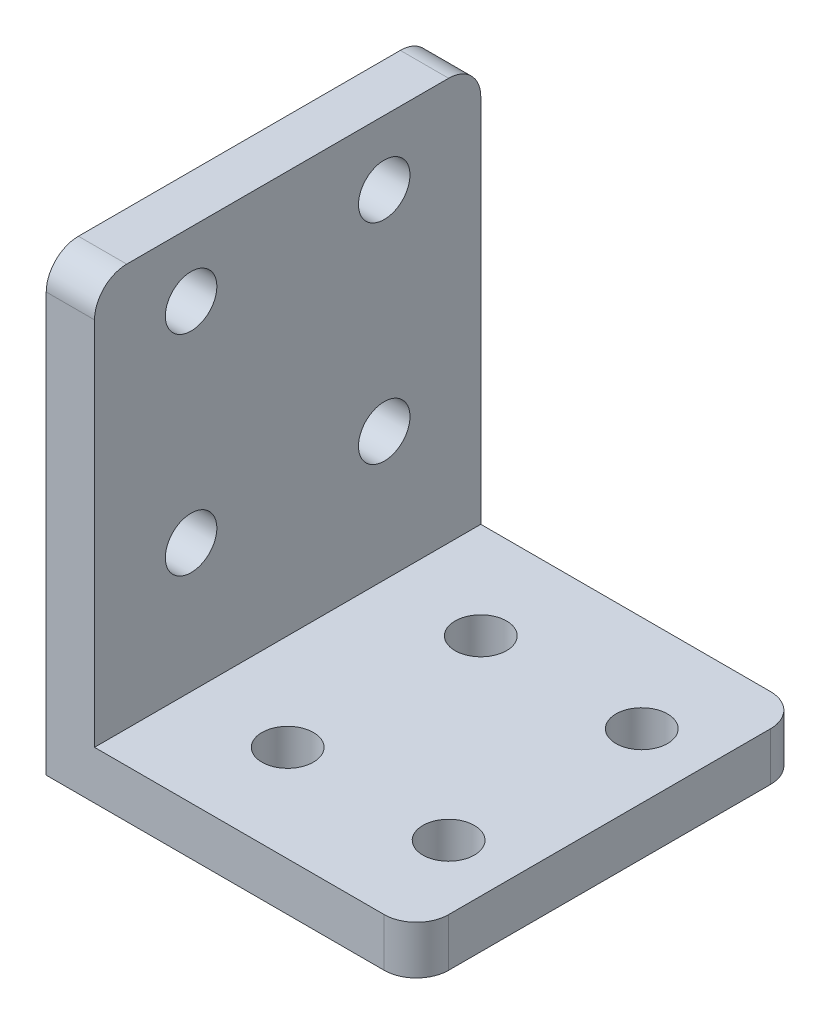
SolidWorks part; units mm, degrees
ref_plane "前视基准面" through (0, 0, 0) normal (0, 0, 1) x (1, 0, 0)
ref_plane "上视基准面" through (0, 0, 0) normal (0, 1, 0) x (1, 0, 0)
ref_plane "右视基准面" through (0, 0, 0) normal (1, 0, 0) x (0, 0, -1)
sketch "草图1" plane through (0, 0, 0) normal (0, 0, 1) x (1, 0, 0)
  line L0 (3, 231.6916) -> (3, 101.6916) construction
  line L1 (3, 129.6916) -> (6, 129.6916)
  line L2 (3, 129.6916) -> (3, -64.3846)
  line L4 (6, 129.6916) -> (6, 104.6916)
  line L6 (3, 101.6916) -> (26, 101.6916)
  line L7 (3, 101.6916) -> (3, -61.5122)
  line L8 (6, 104.6916) -> (26, 104.6916)
  line L9 (26, 101.6916) -> (26, 104.6916)
  dimension "D1" = 3
  dimension "D2" = 3
  dimension "D3" = 25
  dimension "D4" = 20
extrude "凸台-拉伸1" add sketch "草图1" against normal blind 24 contours L6 L9 L8 L4 L1 L2 L7 region at (4.5, 129.3293, 0)
sketch "草图2" plane through (6, 0, 0) normal (1, 0, 0) x (0, 0, -1)
  line L0 (24, 129.6916) -> (0, 129.6916) construction
  line L1 (0, 129.6916) -> (0, 104.6916) construction
  line L2 (24, 129.6916) -> (24, 104.6916) construction
  circle A0 centre (6, 125.6916) radius 1.6
  circle A1 centre (18, 125.6916) radius 1.6
  dimension "D1" = 3.2
  dimension "D2" = 3.2
  dimension "D3" = 4
  dimension "D4" = 6
  dimension "D5" = 6
  dimension "D6" = 4
extrude "切除-拉伸1" cut sketch "草图2" against normal blind 24
sketch "草图3" plane through (0, 104.6916, 0) normal (0, 1, 0) x (1, 0, 0)
  line L0 (26, 24) -> (26, 0) construction
  line L1 (6, 0) -> (26, 0) construction
  line L2 (6, 24) -> (26, 24) construction
  circle A0 centre (22, 6) radius 1.6
  circle A1 centre (22, 18) radius 1.6
  dimension "D1" = 3.2
  dimension "D2" = 3.2
  dimension "D3" = 4
  dimension "D4" = 4
  dimension "D5" = 6
  dimension "D6" = 6
extrude "切除-拉伸2" cut sketch "草图3" against normal blind 24
fillet "圆角1" radius 2 4 edges at (26, 103.1916, -24) (26, 103.1916, 0) (4.5, 129.6916, -24) (4.5, 129.6916, 0)
sketch "草图4" plane through (3, 0, 0) normal (-1, 0, 0) x (0, 0, 1)
  circle A0 centre (-18, 112.6916) radius 1.6
  circle A1 centre (-6, 112.6916) radius 1.6
  point P4 (-18, 112.6916)
  point P5 (-6, 112.6916)
extrude "切除-拉伸3" cut sketch "草图4" against normal blind 4
sketch "草图5" plane through (0, 104.6916, 0) normal (0, 1, 0) x (1, 0, 0)
  line L0 (6, 0) -> (24, 0) construction
  line L1 (22, 18) -> (12, 18) construction
  line L2 (22, 18) -> (22, 6) construction
  line L3 (22, 6) -> (12, 6) construction
  line L4 (12, 18) -> (12, 6) construction
  circle A0 centre (12, 18) radius 1.6
  circle A1 centre (12, 6) radius 1.6
  dimension "D4" = 3.2
  dimension "D1" = 12
  dimension "D2" = 6
  dimension "D3" = 10
extrude "切除-拉伸4" cut sketch "草图5" against normal blind 4
